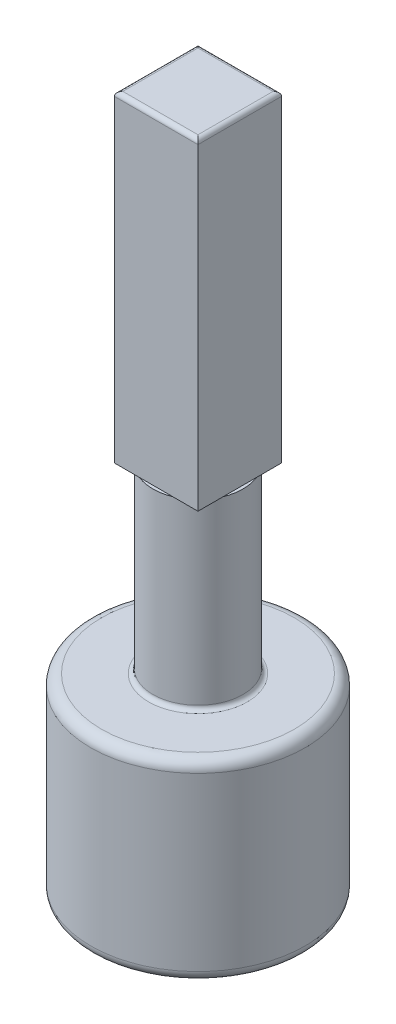
SolidWorks part; units mm, degrees
ref_plane "Front Plane" through (0, 0, 0) normal (0, 0, 1) x (1, 0, 0)
ref_plane "Top Plane" through (0, 0, 0) normal (0, 1, 0) x (1, 0, 0)
ref_plane "Right Plane" through (0, 0, 0) normal (1, 0, 0) x (0, 0, -1)
sketch "Sketch1" plane through (0, 0, 0) normal (0, 1, 0) x (1, 0, 0)
  line L1 (-3.35, 2.6) -> (3.35, 2.6)
  line L2 (-3.35, 2.6) -> (-3.35, -2.6)
  line L3 (-3.35, -2.6) -> (3.35, -2.6)
  line L4 (3.35, 2.6) -> (3.35, -2.6)
  line L5 (-3.35, 2.6) -> (3.35, -2.6) construction
  line L6 (-3.35, -2.6) -> (3.35, 2.6) construction
  circle A1 centre (0, 0) radius 5
  dimension "D2" = 10
  dimension "D1" = 5.2
  dimension "D3" = 6.7
extrude "Boss-Extrude1" add sketch "Sketch1" along normal blind 5
sketch "Sketch2" plane through (0, 5, 0) normal (0, 1, 0) x (1, 0, 0)
  circle A0 centre (0, 0) radius 5
  dimension "D1" = 10
extrude "Boss-Extrude2" add sketch "Sketch2" along normal blind 4
sketch "Sketch3" plane through (0, 9, 0) normal (0, 1, 0) x (1, 0, 0)
  circle A0 centre (0, 0) radius 2.1
  dimension "D1" = 4.2
extrude "Boss-Extrude3" add sketch "Sketch3" along normal blind 8.5
sketch "Sketch4" plane through (0, 17.5, 0) normal (0, 1, 0) x (1, 0, 0)
  line L1 (-1.95, -1.95) -> (1.95, -1.95)
  line L2 (-1.95, -1.95) -> (-1.95, 1.95)
  line L3 (-1.95, 1.95) -> (1.95, 1.95)
  line L4 (1.95, -1.95) -> (1.95, 1.95)
  line L5 (-1.95, -1.95) -> (1.95, 1.95) construction
  line L6 (-1.95, 1.95) -> (1.95, -1.95) construction
  point P0 (0, 0)
  dimension "D1" = 3.9
extrude "Boss-Extrude4" add sketch "Sketch4" along normal blind 15
fillet "Fillet2" radius 0.5 2 edges at (0, 0, 5) (0, 9, 5)
fillet "Fillet3" radius 0.2 4 edges at (0, 32.5, -1.95) (1.95, 32.5, 0) (0, 32.5, 1.95) (-1.95, 32.5, 0)
fillet "Fillet4" radius 0.2 4 edges at (0, 0, -2.6) (3.35, 0, 0) (0, 0, 2.6) (-3.35, 0, 0)
fillet "Fillet5" radius 0.2 1 edges at (0, 9, 2.1)
